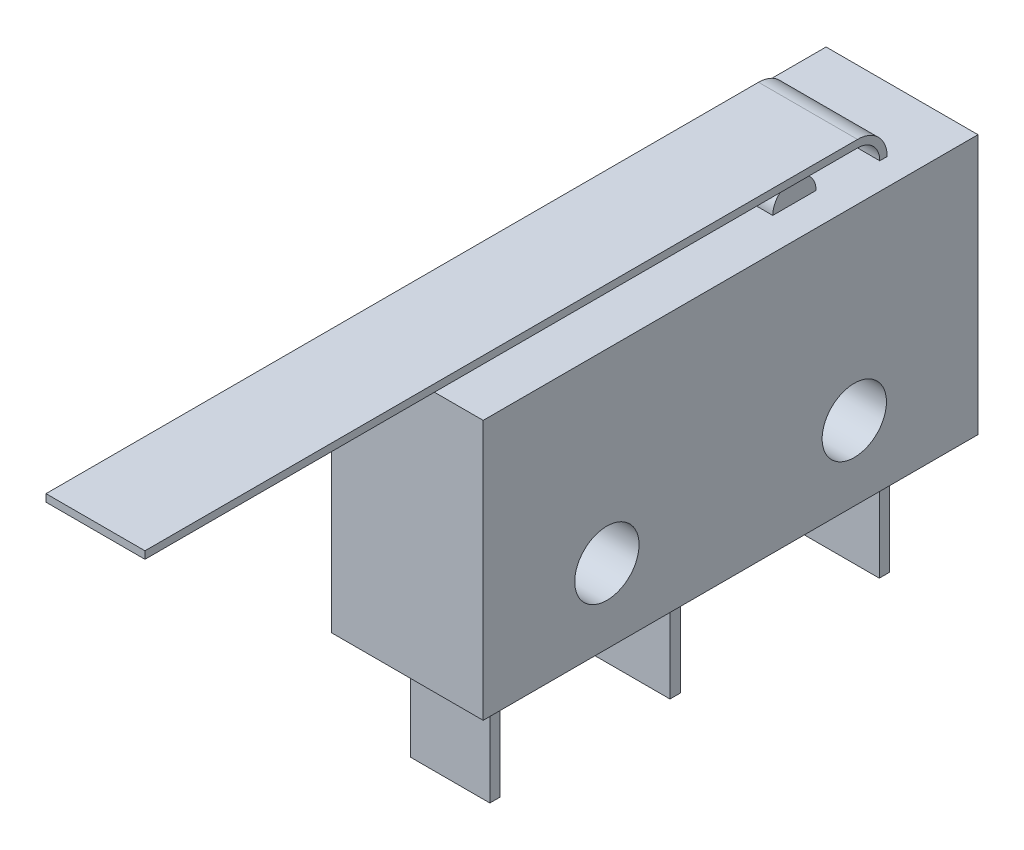
SolidWorks part; units mm, degrees
ref_plane "Front Plane" through (0, 0, 0) normal (0, 0, 1) x (1, 0, 0)
ref_plane "Top Plane" through (0, 0, 0) normal (0, 1, 0) x (1, 0, 0)
ref_plane "Right Plane" through (0, 0, 0) normal (1, 0, 0) x (0, 0, -1)
sketch "Sketch1" plane through (0, 0, 0) normal (1, 0, 0) x (0, 0, -1)
  line L1 (0, 0) -> (20, 0)
  line L2 (0, 0) -> (0, -10.5)
  line L3 (0, -10.5) -> (20, -10.5)
  line L4 (20, 0) -> (20, -10.5)
  circle A0 centre (5, -7.5) radius 1.3
  circle A1 centre (15, -7.5) radius 1.3
  circle A2 centre (5, -7.5) radius 1.3 construction
  circle A3 centre (15, -7.5) radius 1.3 construction
extrude "Boss-Extrude1" add sketch "Sketch1" along normal blind 6.14
ref_plane "Midplane" through (3.07, 0, 0) normal (1, 0, 0) x (0, 0, -1)
sketch "Sketch2" plane through (3.07, 0, 0) normal (1, 0, 0) x (0, 0, -1)
  line L1 (16.2, 0.9) -> (-12.6, 0.9)
  line L2 (-12.6, 0.9) -> (-12.6, 1.2)
  line L3 (-45.2837, 1.2) -> (16.2, 1.2) construction
  line L4 (-12.6, 1.2) -> (16.2, 1.2)
  line L5 (17.4, 0) -> (17.1, 0)
  line L6 (20, 0) -> (0, 0) construction
  arc A0 (17.4, 0) -> (15, 0) centre (16.2, 0) ccw construction
  arc A1 (16.2, 1.2) -> (17.4, 0) centre (16.2, 0) cw
  arc A2 (16.2, 0.9) -> (17.1, 0) centre (16.2, 0) cw
  point P16 (0, 0)
  point P17 (16.2994, 0.094)
  dimension "D1" = 0.3
  dimension "D2" = 30
extrude "Boss-Extrude2" add sketch "Sketch2" along normal mid plane 4
sketch "Sketch3" plane through (3.07, 0, 0) normal (1, 0, 0) x (0, 0, -1)
  line L0 (20, 0) -> (0, 0) construction
  line L2 (-12.6, 0.9) -> (16.2, 0.9) construction
  line L3 (20, -10.5) -> (20, 0) construction
  line L5 (13.025, 0) -> (14.775, 0)
  arc A0 (13, 0) -> (14.8, 0) centre (13.9, 0) cw construction
  arc A1 (13.025, 0) -> (14.775, 0) centre (13.9, 0) cw
  dimension "D1" = 7
  dimension "D2" = 0.025
extrude "Boss-Extrude5" add sketch "Sketch3" along normal mid plane 3.5
sketch "Sketch4" plane through (3.07, 0, 0) normal (1, 0, 0) x (0, 0, -1)
  line L0 (0, -10.5) -> (20, -10.5) construction
  line L1 (2.16, -10.5) -> (1.74, -10.5)
  line L2 (2.16, -10.5) -> (2.16, -15)
  line L3 (2.16, -15) -> (1.74, -15)
  line L4 (1.74, -10.5) -> (1.74, -15)
  line L5 (1.74, -15) -> (9.02, -15) construction
  line L6 (9.02, -10.5) -> (9.44, -10.5)
  line L7 (9.02, -10.5) -> (9.02, -15)
  line L8 (9.02, -15) -> (9.44, -15)
  line L9 (9.44, -10.5) -> (9.44, -15)
  line L10 (17.48, -10.5) -> (17.9, -10.5)
  line L11 (17.48, -10.5) -> (17.48, -15)
  line L12 (17.48, -15) -> (17.9, -15)
  line L13 (17.9, -10.5) -> (17.9, -15)
  line L14 (9.44, -15) -> (17.48, -15) construction
  dimension "D1" = 4.5
  dimension "D2" = 2.16
  dimension "D3" = 9.44
  dimension "D4" = 17.9
  dimension "D5" = 0.42
extrude "Boss-Extrude6" add sketch "Sketch4" along normal mid plane 3.2
